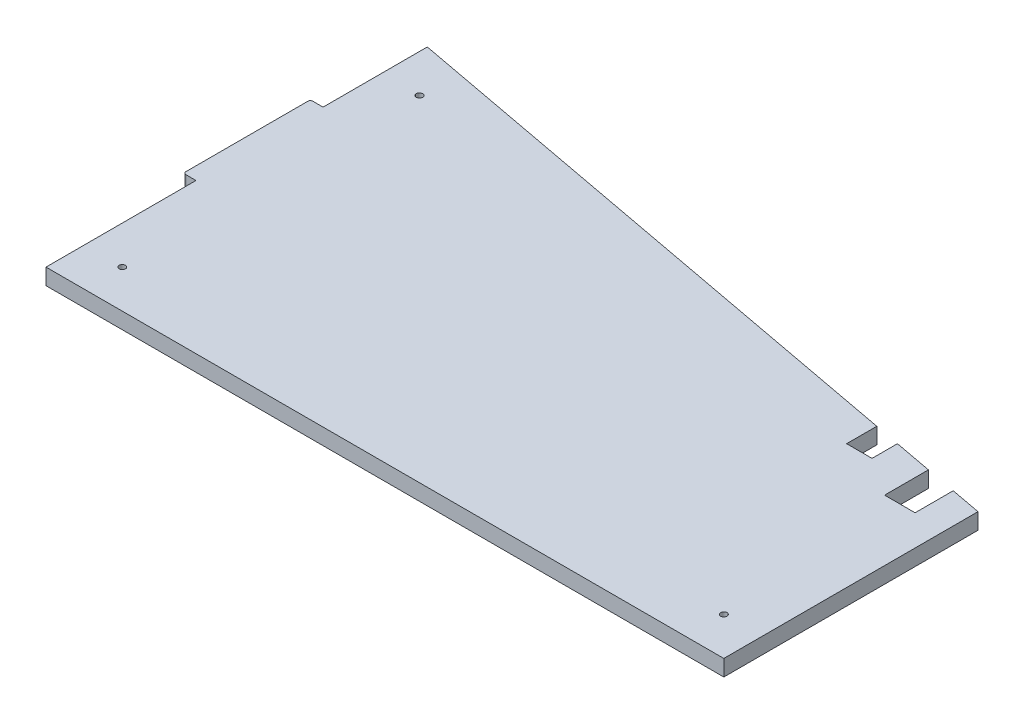
SolidWorks part; units mm, degrees
material "Balsa"
ref_plane "Front Plane" through (0, 0, 0) normal (0, 0, 1) x (1, 0, 0)
ref_plane "Top Plane" through (0, 0, 0) normal (0, 1, 0) x (1, 0, 0)
ref_plane "Right Plane" through (0, 0, 0) normal (1, 0, 0) x (0, 0, -1)
sketch "Sketch2" plane through (0, 0, 0) normal (0, 1, 0) x (1, 0, 0)
  line L0 (0, 0) -> (266.65, 0)
  line L1 (266.65, 0) -> (266.65, 100)
  line L2 (266.65, 100) -> (254.65, 102.2501)
  line L3 (0, 150) -> (0, 109)
  line L4 (242.65, 104.5003) -> (242.65, 87.2501)
  line L5 (242.65, 87.2501) -> (254.65, 87.2501)
  line L6 (254.65, 87.2501) -> (254.65, 102.2501)
  line L7 (242.65, 104.5003) -> (227.65, 107.313)
  line L8 (227.65, 97.313) -> (217.65, 97.313)
  line L9 (217.65, 97.313) -> (217.65, 109.1881)
  line L10 (227.65, 97.313) -> (227.65, 107.313)
  line L11 (217.65, 109.1881) -> (0, 150)
  line L12 (0, 59) -> (-4, 59)
  line L13 (-5, 60) -> (-5, 108)
  line L14 (-4, 109) -> (0, 109)
  line L15 (0, 59) -> (0, 0)
  arc A0 (-4, 59) -> (-5, 60) centre (-4, 60) cw
  arc A1 (-5, 108) -> (-4, 109) centre (-4, 108) cw
  circle A2 centre (15, 15) radius 1.25
  circle A3 centre (251.65, 15) radius 1.25
  circle A4 centre (15, 131.9259) radius 1.25
  point P20 (-5, 59)
  point P23 (-5, 109)
  point P28 (0, 0)
  dimension "D13" = 1
  dimension "D14" = 2.5
  dimension "D15" = 2.5
  dimension "D16" = 2.5
  dimension "D1" = 150
  dimension "D2" = 100
  dimension "D3" = 266.65
  dimension "D4" = 12
  dimension "D5" = 12
  dimension "D6" = 15
  dimension "D7" = 10
  dimension "D8" = 10
  dimension "D9" = 15
  dimension "D10" = 5
  dimension "D11" = 59
  dimension "D12" = 50
  dimension "D17" = 15
  dimension "D18" = 15
  dimension "D19" = 15
  dimension "D20" = 15
  dimension "D21" = 15
  dimension "D22" = 15
extrude "Boss-Extrude1" add sketch "Sketch2" along normal blind 6.35
